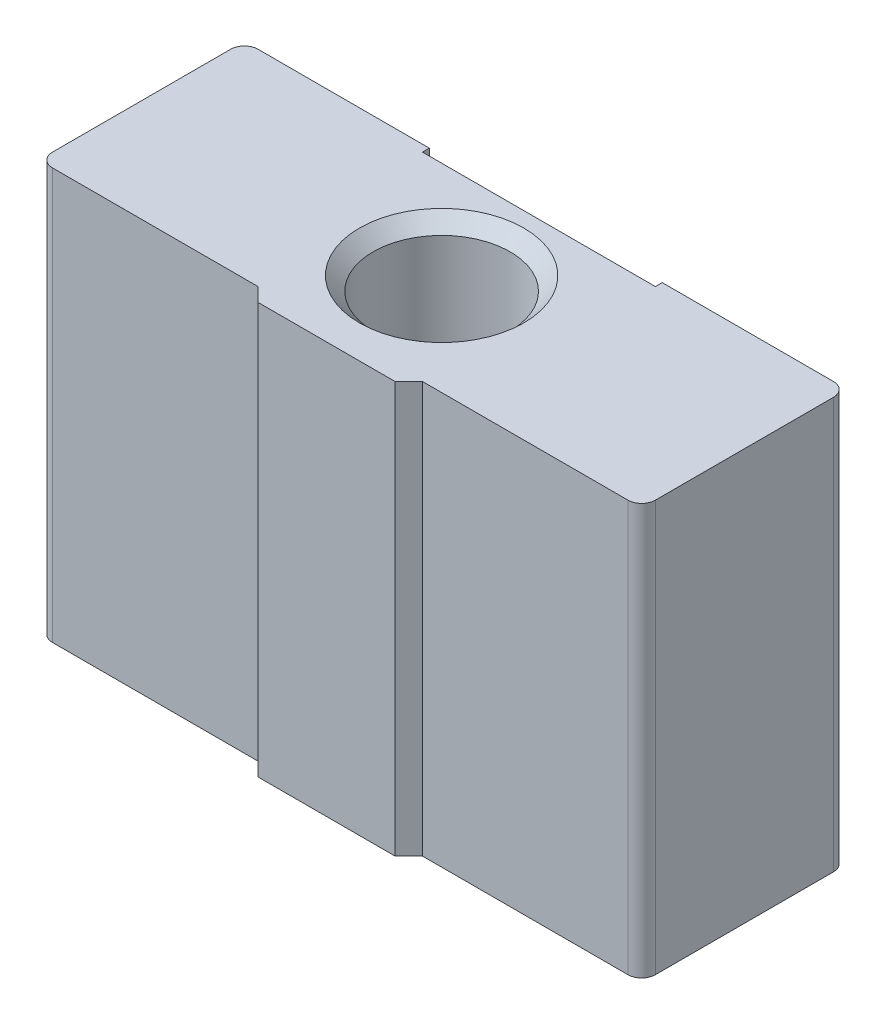
SolidWorks part; units mm, degrees
material "1.4511 (X3CrNb17)"
ref_plane "前视基准面" through (0, 0, 0) normal (0, 0, 1) x (1, 0, 0)
ref_plane "上视基准面" through (0, 0, 0) normal (0, 1, 0) x (1, 0, 0)
ref_plane "右视基准面" through (0, 0, 0) normal (1, 0, 0) x (0, 0, -1)
sketch "草图1" plane through (0, 0, 0) normal (0, 1, 0) x (1, 0, 0)
  line L0 (-22, 0) -> (22, 0)
  line L1 (-22, 0) -> (-22, -15)
  line L2 (-22, -15) -> (-5, -15)
  line L3 (22, -15) -> (22, 0)
  line L4 (0, 25.5325) -> (0, -25.5325) construction
  line L5 (5, -15) -> (22, -15)
  line L9 (-5, -16) -> (5, -16)
  line L10 (-5, -16) -> (-5, -15)
  line L11 (5, -16) -> (5, -15)
  point P4 (0, 0)
  point P10 (0, 0)
  point P12 (0, -16)
  dimension "D3" = 10
  dimension "D1" = 44
  dimension "D2" = 15
  dimension "D4" = 1
extrude "凸台-拉伸1" add sketch "草图1" along normal blind 30
sketch "草图2" plane through (0, 0, 0) normal (0, -1, 0) x (1, 0, 0)
  line L0 (0, -25.5325) -> (0, 25.5325) construction
  circle A1 centre (0, 7.6) radius 5
  dimension "D1" = 10
  dimension "D2" = 7.6
extrude "切除-拉伸1" cut sketch "草图2" against normal blind 30
sketch "草图3" plane through (0, 0, 0) normal (0, 0, -1) x (-1, 0, 0)
  line L0 (-22, 0) -> (22, 0) construction
  line L1 (-16, 24) -> (16, 24) construction
  line L2 (-16, 24) -> (-16, 6) construction
  line L3 (-16, 6) -> (16, 6) construction
  line L4 (16, 24) -> (16, 6) construction
  line L5 (-22, 30) -> (-22, 0) construction
  dimension "D1" = 32
  dimension "D2" = 18
  dimension "D3" = 6
  dimension "D4" = 6
hole_wizard "M5X0.5 螺纹孔的螺纹孔钻头1" positions "草图4" profile "草图6" hole size "M5X0.5" standard "GB"
sketch "草图4" plane through (0, 0, 0) normal (0, 0, -1) x (-1, 0, 0)
  point P0 (-16, 24)
  point P3 (16, 24)
  point P6 (16, 6)
  point P9 (-16, 6)
sketch "草图6" plane through (16, 24, 0) normal (1, 0, 0) x (0, 1, 0)
  line L0 (0, 0) -> (0, 11.3519)
  line L1 (0, 11.3519) -> (2.25, 10)
  line L2 (2.25, 10) -> (2.25, 0)
  line L5 (2.25, 0) -> (0, 0)
  line L10 (0, 11.3519) -> (-2.25, 10) construction
  line L11 (0, -6.35) -> (0, 107.95) construction
  dimension "孔直径" = 4.5
  dimension "孔深度" = 10
  dimension "导头角度" = 118
sketch "草图7" plane through (0, 0, 0) normal (0, -1, 0) x (1, 0, 0)
  line L0 (-8.5, 0) -> (8.5, 0)
  line L1 (22, 0) -> (-22, 0) construction
  line L2 (-8.5, 0) -> (-8.5, 0.5)
  line L3 (-8.5, 0.5) -> (8.5, 0.5)
  line L4 (8.5, 0.5) -> (8.5, 0)
  point P6 (0, 0)
  dimension "D1" = 17
  dimension "D2" = 0.5
extrude "切除-拉伸2" cut sketch "草图7" against normal through all
chamfer "倒角1" distance 1 angle 45 4 edges at (-5, 15, 15) (5, 15, 15) (0, 30, 2.6) (0, 0, 2.6)
fillet "圆角1" radius 1 4 edges at (-22, 15, 15) (-22, 15, 0) (22, 15, 0) (22, 15, 15)
